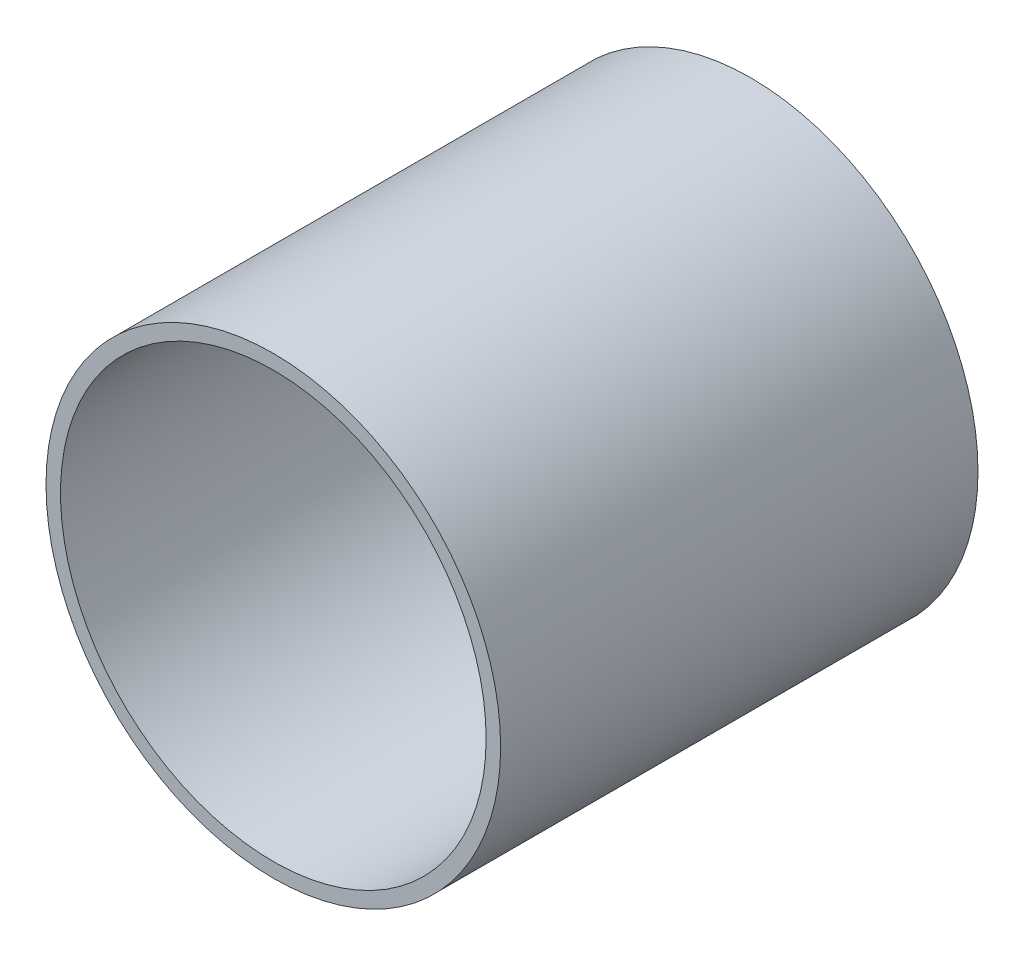
SolidWorks part; units mm, degrees
material "ABS"
ref_plane "Front Plane" through (0, 0, 0) normal (0, 0, 1) x (1, 0, 0)
ref_plane "Top Plane" through (0, 0, 0) normal (0, 1, 0) x (1, 0, 0)
ref_plane "Right Plane" through (0, 0, 0) normal (1, 0, 0) x (0, 0, -1)
sketch "Sketch1" plane through (0, 0, 0) normal (0, 1, 0) x (1, 0, 0)
  line L1 (0, 0) -> (-300, 0)
  line L2 (0, 0) -> (0, -170)
  line L3 (0, -170) -> (-300, -170)
  line L4 (-300, 0) -> (-300, -170)
  dimension "D1" = 300
  dimension "D2" = 170
extrude "Boss-Extrude1" add sketch "Sketch1" along normal blind 225
shell "Shell1" thickness 10 removed face at (-150, 112.5, 170)
sketch "Sketch2" plane through (0, 0, 10) normal (0, 0, 1) x (1, 0, 0)
  line L0 (-290, 112.5) -> (-10, 112.5) construction
  line L1 (-290, 215) -> (-290, 10) construction
  line L2 (-10, 215) -> (-10, 10) construction
  circle A0 centre (-150, 112.5) radius 6.5
  dimension "D1" = 13
  dimension "D2" = 140
extrude "Cut-Extrude1" cut sketch "Sketch2" against normal blind 10
sketch "Sketch3" plane through (0, 0, 10) normal (0, 0, 1) x (1, 0, 0)
  line L0 (-150, 112.5) -> (-150, 135) construction
  line L1 (-150, 112.5) -> (-134.0901, 128.4099) construction
  circle A0 centre (-150, 112.5) radius 22.5 construction
  dimension "D1" = 45
  dimension "D2" = 45
hole_wizard "M5 Clearance Hole1" positions "Sketch4" profile "Sketch5" hole size "M5" standard "ANSI Metric"
sketch "Sketch4" plane through (0, 0, 10) normal (0, 0, 1) x (1, 0, 0)
  point P0 (-134.0901, 128.4099)
sketch "Sketch5" plane through (-134.0901, 128.4099, 10) normal (1, 0, 0) x (0, -1, 0)
  line L0 (0, 0) -> (0, 21.6524)
  line L1 (0, 21.6524) -> (2.75, 20)
  line L2 (2.75, 20) -> (2.75, 0.025)
  line L3 (2.75, 0.025) -> (2.775, 0)
  line L5 (2.775, 0) -> (0, 0)
  line L6 (-2.75, 0.025) -> (-2.775, 0) construction
  line L10 (0, 21.6524) -> (-2.75, 20) construction
  line L11 (0, -6.35) -> (0, 107.95) construction
  dimension "Hole Dia." = 5.5
  dimension "Hole Depth" = 20
  dimension "Near C'Sink Dia." = 5.55
  dimension "Near C'Sink Angle" = 90
  dimension "Drill Angle" = 118
pattern_circular "CirPattern1" count 4 over 360 about axis through (-150, 112.5, 10) along (0, 0, 1) of "M5 Clearance Hole1"
sketch "Sketch6" plane through (0, 0, 0) normal (0, 0, -1) x (-1, 0, 0)
  circle A0 centre (150, 112.5) radius 100
  dimension "D1" = 200
extrude "Cut-Extrude2" cut sketch "Sketch6" against normal through all flip side to cut
sketch "Sketch7" plane through (0, 0, 10) normal (0, 0, 1) x (1, 0, 0)
  circle A0 centre (-150, 112.5) radius 93.619
  circle A2 centre (-150, 112.5) radius 100
extrude "Boss-Extrude2" add sketch "Sketch7" along normal blind 200
